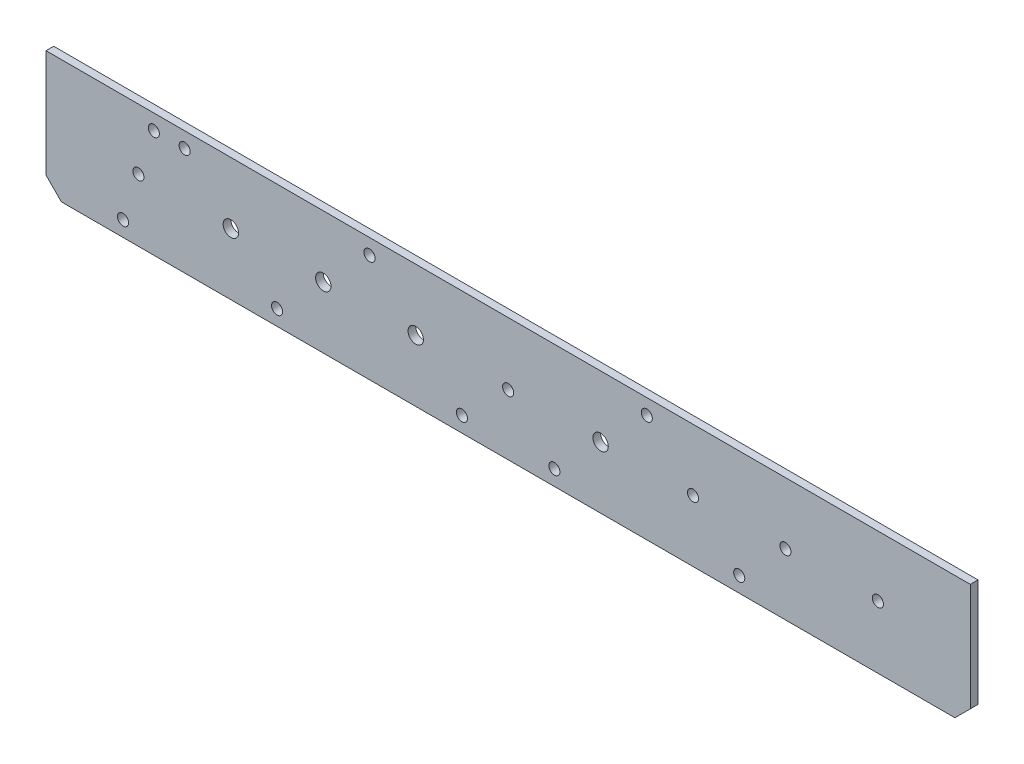
SolidWorks part; units mm, degrees
ref_plane "Front Plane" through (0, 0, 0) normal (0, 0, 1) x (1, 0, 0)
ref_plane "Top Plane" through (0, 0, 0) normal (0, 1, 0) x (1, 0, 0)
ref_plane "Right Plane" through (0, 0, 0) normal (1, 0, 0) x (0, 0, -1)
sketch "Sketch1" plane through (0, 0, 0) normal (0, 0, 1) x (1, 0, 0)
  line L1 (0, 0) -> (381, 0)
  line L2 (0, 0) -> (0, 50.8)
  line L3 (0, 50.8) -> (381, 50.8)
  line L4 (381, 0) -> (381, 50.8)
  dimension "D1" = 50.8
  dimension "D2" = 381
extrude "Boss-Extrude1" add sketch "Sketch1" along normal blind 3.175
sketch "Sketch2" plane through (0, 0, 3.175) normal (0, 0, 1) x (1, 0, 0)
  line L0 (190.5, 25.0031) -> (38.1, 25.7969) construction
  line L1 (190.5, 50.8) -> (190.5, 0) construction
  line L2 (381, 50.8) -> (0, 50.8) construction
  line L3 (0, 0) -> (381, 0) construction
  line L4 (190.5, 25.0031) -> (342.9, 25.7969) construction
  line L5 (0, 6.35) -> (0, 0)
  line L6 (0, 50.8) -> (0, 0) construction
  line L7 (0, 0) -> (6.35, 0)
  line L8 (6.35, 0) -> (0, 6.35)
  line L9 (381, 0) -> (374.65, 0)
  line L10 (374.65, 0) -> (381, 6.35)
  line L11 (381, 6.35) -> (381, 0)
  circle A0 centre (38.1, 25.7969) radius 2.286
  circle A1 centre (190.5, 25.0031) radius 2.286
  circle A2 centre (114.3, 25.4) radius 3.175
  circle A3 centre (76.2, 25.4) radius 3.175
  circle A4 centre (152.4, 25.4) radius 3.175
  circle A5 centre (228.6, 25.4) radius 3.175
  circle A6 centre (304.8, 25.4) radius 2.286
  circle A7 centre (266.7, 25.4) radius 2.286
  circle A8 centre (342.9, 25.7969) radius 2.286
  circle A9 centre (57.15, 44.45) radius 2.286
  circle A10 centre (171.45, 6.35) radius 2.286
  circle A11 centre (209.55, 6.35) radius 2.286
  circle A13 centre (133.35, 44.45) radius 2.286
  circle A14 centre (247.65, 44.45) radius 2.286
  circle A15 centre (95.25, 6.35) radius 2.286
  circle A16 centre (285.75, 6.35) radius 2.286
  circle A17 centre (44.45, 44.45) radius 2.286
  circle A18 centre (31.75, 6.35) radius 2.286
  point P17 (190.5, 25.4)
  dimension "D2" = 4.572
  dimension "D5" = 6.35
  dimension "D7" = 4.572
  dimension "D12" = 4.572
  dimension "D15" = 4.572
  dimension "D16" = 4.572
  dimension "D19" = 4.572
  dimension "D21" = 6.35
  dimension "D1" = 0.7937
  dimension "D3" = 38.1
  dimension "D4" = 152.4
  dimension "D6" = 38.1
  dimension "D8" = 57.15
  dimension "D9" = 19.05
  dimension "D10" = 57.15
  dimension "D11" = 19.05
  dimension "D13" = 57.15
  dimension "D14" = 19.05
  dimension "D17" = 19.05
  dimension "D18" = 19.05
  dimension "D20" = 19.05
  dimension "D22" = 6.35
  dimension "D23" = 6.35
  dimension "D24" = 6.35
extrude "Cut-Extrude1" cut sketch "Sketch2" against normal up to next
